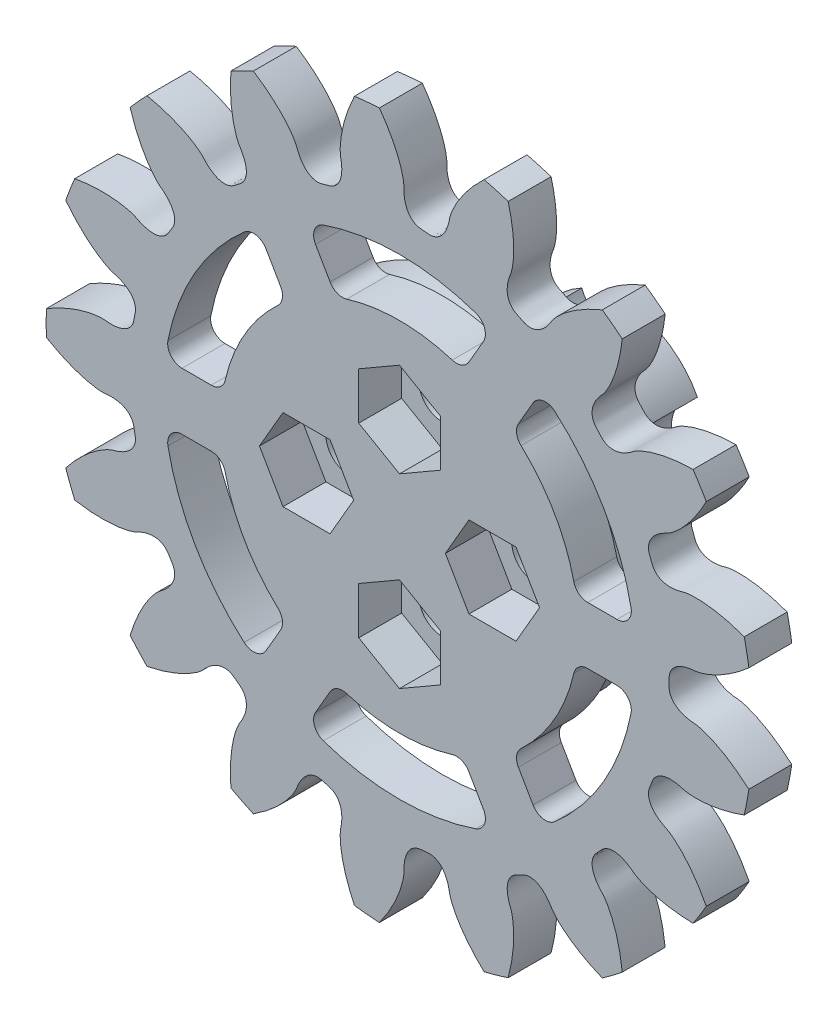
SolidWorks part; units mm, degrees
material "ABS"
ref_plane "前视基准面" through (0, 0, 0) normal (0, 0, 1) x (1, 0, 0)
ref_plane "上视基准面" through (0, 0, 0) normal (0, 1, 0) x (1, 0, 0)
ref_plane "右视基准面" through (0, 0, 0) normal (1, 0, 0) x (0, 0, -1)
sketch "草图1" plane through (0, 0, 0) normal (0, 0, 1) x (1, 0, 0)
  arc A0 (14.1766, -20.2266) -> (15.5749, -19.1706) centre (0, 0) ccw
  arc A1 (20.5259, -13.7396) -> (21.4484, -12.2498) centre (0, 0) ccw
  arc A2 (24.1032, -5.397) -> (24.4251, -3.6746) centre (0, 0) ccw
  arc A3 (24.4251, 3.6746) -> (24.1032, 5.397) centre (0, 0) ccw
  arc A4 (21.4484, 12.2498) -> (20.5259, 13.7396) centre (0, 0) ccw
  arc A5 (15.5749, 19.1706) -> (14.1766, 20.2266) centre (0, 0) ccw
  arc A6 (7.5979, 23.5024) -> (5.9126, 23.9819) centre (0, 0) ccw
  arc A7 (-1.4052, 24.66) -> (-3.15, 24.4983) centre (0, 0) ccw
  arc A8 (-10.2185, 22.4871) -> (-11.7871, 21.7061) centre (0, 0) ccw
  arc A9 (-17.6518, 17.2773) -> (-18.8323, 15.9824) centre (0, 0) ccw
  arc A10 (-22.7011, 9.734) -> (-23.3341, 8.1001) centre (0, 0) ccw
  arc A11 (-24.6845, 0.8761) -> (-24.6845, -0.8761) centre (0, 0) ccw
  arc A12 (-23.3341, -8.1001) -> (-22.7011, -9.734) centre (0, 0) ccw
  arc A13 (-18.8323, -15.9824) -> (-17.6518, -17.2773) centre (0, 0) ccw
  arc A14 (-11.7871, -21.7061) -> (-10.2185, -22.4871) centre (0, 0) ccw
  arc A15 (-3.15, -24.4983) -> (-1.4052, -24.66) centre (0, 0) ccw
  arc A16 (5.9126, -23.9819) -> (7.5979, -23.5024) centre (0, 0) ccw
  spline S0 degree 3 number of poles 73 (7.5979, -23.5024) -> (14.1766, -20.2266)
  spline S1 degree 3 number of poles 73 (15.5749, -19.1706) -> (20.5259, -13.7396)
  spline S2 degree 3 number of poles 73 (21.4484, -12.2498) -> (24.1032, -5.397)
  spline S3 degree 3 number of poles 73 (24.4251, -3.6746) -> (24.4251, 3.6746)
  spline S4 degree 3 number of poles 73 (24.1032, 5.397) -> (21.4484, 12.2498)
  spline S5 degree 3 number of poles 73 (20.5259, 13.7396) -> (15.5749, 19.1706)
  spline S6 degree 3 number of poles 73 (14.1766, 20.2266) -> (7.5979, 23.5024)
  spline S7 degree 3 number of poles 73 (5.9126, 23.9819) -> (-1.4052, 24.66)
  spline S8 degree 3 number of poles 73 (-3.15, 24.4983) -> (-10.2185, 22.4871)
  spline S9 degree 3 number of poles 73 (-11.7871, 21.7061) -> (-17.6518, 17.2773)
  spline S10 degree 3 number of poles 73 (-18.8323, 15.9824) -> (-22.7011, 9.734)
  spline S11 degree 3 number of poles 73 (-23.3341, 8.1001) -> (-24.6845, 0.8761)
  spline S12 degree 3 number of poles 73 (-24.6845, -0.8761) -> (-23.3341, -8.1001)
  spline S13 degree 3 number of poles 73 (-22.7011, -9.734) -> (-18.8323, -15.9824)
  spline S14 degree 3 number of poles 73 (-17.6518, -17.2773) -> (-11.7871, -21.7061)
  spline S15 degree 3 number of poles 73 (-10.2185, -22.4871) -> (-3.15, -24.4983)
  spline S16 degree 3 number of poles 73 (-1.4052, -24.66) -> (5.9126, -23.9819)
  dimension "D1" = 0
extrude "凸台-拉伸1" add sketch "草图1" along normal blind 5
sketch "草图2" plane through (0, 0, 0) normal (0, 0, -1) x (-1, 0, 0)
  circle A0 centre (0, 0) radius 10
  dimension "D1" = 20
extrude "凸台-拉伸2" add sketch "草图2" along normal blind 2.5
sketch "草图3" plane through (0, 0, 5) normal (0, 0, 1) x (1, 0, 0)
  line L0 (-16.5, 0) -> (-12.5, 0)
  line L1 (-8.25, 14.2894) -> (0, 0)
  line L2 (-16.5, -2) -> (-12.5, -2)
  line L3 (-9.9821, 13.2894) -> (-1.7321, -1)
  line L4 (-16.5, 2) -> (-12.5, 2)
  line L5 (-6.5179, 15.2894) -> (1.7321, 1)
  line L6 (-12.5, 2) -> (-8.75, 2)
  circle A0 centre (0, 0) radius 12.5
  circle A1 centre (0, 0) radius 16.5
  dimension "D1" = 25
  dimension "D2" = 4
  dimension "D3" = 60
  dimension "D4" = 2
  dimension "D5" = 2
extrude "切除-拉伸1" cut sketch "草图3" against normal blind 12 contours L3 A1 L4 L6 A0 region at (-12.3527, 7.1318, 5)
fillet "圆角1" radius 1 4 edges at (-12.339, 2, 2.5) (-9.9212, 13.1841, 2.5) (-7.9015, 9.6859, 2.5) (-16.3783, 2, 2.5)
pattern_circular "阵列(圆周)1" count 6 over 360 about axis through (0, 0, -2.5) along (0, 0, 1) of "圆角1", "切除-拉伸1"
sketch "草图4" plane through (0, 0, 0) normal (0, 0, -1) x (-1, 0, 0)
  circle A0 centre (0, 0) radius 12
  circle A1 centre (0, 0) radius 10 construction
  dimension "D1" = 2
extrude "凸台-拉伸3" add sketch "草图4" along normal blind 2.5
sketch "草图5" plane through (0, 0, -2.5) normal (0, 0, -1) x (-1, 0, 0)
  circle A0 centre (0, 0) radius 6
  circle A1 centre (0, 0) radius 3
  dimension "D1" = 12
  dimension "D2" = 6
extrude "凸台-拉伸4" add sketch "草图5" along normal blind 10
sketch "草图6" plane through (0, 0, -2.5) normal (0, 0, -1) x (-1, 0, 0)
  circle A0 centre (0, 0) radius 10
  circle A1 centre (0, 0) radius 6
  dimension "D1" = 20
extrude "凸台-拉伸6" add sketch "草图6" along normal blind 1.9
sketch "草图7" plane through (0, 0, 5) normal (0, 0, 1) x (1, 0, 0)
  arc A17 (14.1766, -20.2266) -> (15.5749, -19.1706) centre (0, 0) ccw
  arc A18 (20.5259, -13.7396) -> (21.4484, -12.2498) centre (0, 0) ccw
  arc A19 (24.1032, -5.397) -> (24.4251, -3.6746) centre (0, 0) ccw
  arc A20 (24.4251, 3.6746) -> (24.1032, 5.397) centre (0, 0) ccw
  arc A21 (21.4484, 12.2498) -> (20.5259, 13.7396) centre (0, 0) ccw
  arc A22 (15.5749, 19.1706) -> (14.1766, 20.2266) centre (0, 0) ccw
  arc A23 (7.5979, 23.5024) -> (5.9126, 23.9819) centre (0, 0) ccw
  arc A24 (-1.4052, 24.66) -> (-3.15, 24.4983) centre (0, 0) ccw
  arc A25 (-10.2185, 22.4871) -> (-11.7871, 21.7061) centre (0, 0) ccw
  arc A26 (-17.6518, 17.2773) -> (-18.8323, 15.9824) centre (0, 0) ccw
  arc A27 (-22.7011, 9.734) -> (-23.3341, 8.1001) centre (0, 0) ccw
  arc A28 (-24.6845, 0.8761) -> (-24.6845, -0.8761) centre (0, 0) ccw
  arc A29 (-23.3341, -8.1001) -> (-22.7011, -9.734) centre (0, 0) ccw
  arc A30 (-18.8323, -15.9824) -> (-17.6518, -17.2773) centre (0, 0) ccw
  arc A31 (-11.7871, -21.7061) -> (-10.2185, -22.4871) centre (0, 0) ccw
  arc A32 (-3.15, -24.4983) -> (-1.4052, -24.66) centre (0, 0) ccw
  arc A33 (5.9126, -23.9819) -> (7.5979, -23.5024) centre (0, 0) ccw
  arc A34 (14.1766, -20.2266) -> (15.5749, -19.1706) centre (0, 0) ccw
  arc A35 (20.5259, -13.7396) -> (21.4484, -12.2498) centre (0, 0) ccw
  arc A36 (24.1032, -5.397) -> (24.4251, -3.6746) centre (0, 0) ccw
  arc A37 (24.4251, 3.6746) -> (24.1032, 5.397) centre (0, 0) ccw
  arc A38 (21.4484, 12.2498) -> (20.5259, 13.7396) centre (0, 0) ccw
  arc A39 (15.5749, 19.1706) -> (14.1766, 20.2266) centre (0, 0) ccw
  arc A40 (7.5979, 23.5024) -> (5.9126, 23.9819) centre (0, 0) ccw
  arc A41 (-1.4052, 24.66) -> (-3.15, 24.4983) centre (0, 0) ccw
  arc A42 (-10.2185, 22.4871) -> (-11.7871, 21.7061) centre (0, 0) ccw
  arc A43 (-17.6518, 17.2773) -> (-18.8323, 15.9824) centre (0, 0) ccw
  arc A44 (-22.7011, 9.734) -> (-23.3341, 8.1001) centre (0, 0) ccw
  arc A45 (-24.6845, 0.8761) -> (-24.6845, -0.8761) centre (0, 0) ccw
  arc A46 (-23.3341, -8.1001) -> (-22.7011, -9.734) centre (0, 0) ccw
  arc A47 (-18.8323, -15.9824) -> (-17.6518, -17.2773) centre (0, 0) ccw
  arc A48 (-11.7871, -21.7061) -> (-10.2185, -22.4871) centre (0, 0) ccw
  arc A49 (-3.15, -24.4983) -> (-1.4052, -24.66) centre (0, 0) ccw
  arc A50 (5.9126, -23.9819) -> (7.5979, -23.5024) centre (0, 0) ccw
  spline S17 degree 3 number of poles 73 (7.5979, -23.5024) -> (14.1766, -20.2266)
  spline S18 degree 3 number of poles 73 (15.5749, -19.1706) -> (20.5259, -13.7396)
  spline S19 degree 3 number of poles 73 (21.4484, -12.2498) -> (24.1032, -5.397)
  spline S20 degree 3 number of poles 73 (24.4251, -3.6746) -> (24.4251, 3.6746)
  spline S21 degree 3 number of poles 73 (24.1032, 5.397) -> (21.4484, 12.2498)
  spline S22 degree 3 number of poles 73 (20.5259, 13.7396) -> (15.5749, 19.1706)
  spline S23 degree 3 number of poles 73 (14.1766, 20.2266) -> (7.5979, 23.5024)
  spline S24 degree 3 number of poles 73 (5.9126, 23.9819) -> (-1.4052, 24.66)
  spline S25 degree 3 number of poles 73 (-3.15, 24.4983) -> (-10.2185, 22.4871)
  spline S26 degree 3 number of poles 73 (-11.7871, 21.7061) -> (-17.6518, 17.2773)
  spline S27 degree 3 number of poles 73 (-18.8323, 15.9824) -> (-22.7011, 9.734)
  spline S28 degree 3 number of poles 73 (-23.3341, 8.1001) -> (-24.6845, 0.8761)
  spline S29 degree 3 number of poles 73 (-24.6845, -0.8761) -> (-23.3341, -8.1001)
  spline S30 degree 3 number of poles 73 (-22.7011, -9.734) -> (-18.8323, -15.9824)
  spline S31 degree 3 number of poles 73 (-17.6518, -17.2773) -> (-11.7871, -21.7061)
  spline S32 degree 3 number of poles 73 (-10.2185, -22.4871) -> (-3.15, -24.4983)
  spline S33 degree 3 number of poles 73 (-1.4052, -24.66) -> (5.9126, -23.9819)
  spline S34 degree 3 number of poles 73 (7.5979, -23.5024) -> (14.1766, -20.2266)
  spline S35 degree 3 number of poles 73 (15.5749, -19.1706) -> (20.5259, -13.7396)
  spline S36 degree 3 number of poles 73 (21.4484, -12.2498) -> (24.1032, -5.397)
  spline S37 degree 3 number of poles 73 (24.4251, -3.6746) -> (24.4251, 3.6746)
  spline S38 degree 3 number of poles 73 (24.1032, 5.397) -> (21.4484, 12.2498)
  spline S39 degree 3 number of poles 73 (20.5259, 13.7396) -> (15.5749, 19.1706)
  spline S40 degree 3 number of poles 73 (14.1766, 20.2266) -> (7.5979, 23.5024)
  spline S41 degree 3 number of poles 73 (5.9126, 23.9819) -> (-1.4052, 24.66)
  spline S42 degree 3 number of poles 73 (-3.15, 24.4983) -> (-10.2185, 22.4871)
  spline S43 degree 3 number of poles 73 (-11.7871, 21.7061) -> (-17.6518, 17.2773)
  spline S44 degree 3 number of poles 73 (-18.8323, 15.9824) -> (-22.7011, 9.734)
  spline S45 degree 3 number of poles 73 (-23.3341, 8.1001) -> (-24.6845, 0.8761)
  spline S46 degree 3 number of poles 73 (-24.6845, -0.8761) -> (-23.3341, -8.1001)
  spline S47 degree 3 number of poles 73 (-22.7011, -9.734) -> (-18.8323, -15.9824)
  spline S48 degree 3 number of poles 73 (-17.6518, -17.2773) -> (-11.7871, -21.7061)
  spline S49 degree 3 number of poles 73 (-10.2185, -22.4871) -> (-3.15, -24.4983)
  spline S50 degree 3 number of poles 73 (-1.4052, -24.66) -> (5.9126, -23.9819)
  dimension "D1" = 0
extrude "切除-拉伸2" cut sketch "草图7" against normal blind 2
sketch "草图8" plane through (0, 0, -4.4) normal (0, 0, -1) x (-1, 0, 0)
  circle A0 centre (0, 0) radius 6.5
  circle A1 centre (-6.5, 0) radius 1.65
  circle A2 centre (-6.5, 0) radius 3
  circle M2 centre (0, 0) radius 6
  dimension "D1" = 3.3
  dimension "D2" = 13
  dimension "D3" = 6
extrude "切除-拉伸3" cut sketch "草图8" against normal mid plane 30 contours A0 A1 | A1 A0 M2 | A1 M2 region at (6.1858, 0, -4.4) region at (7.1612, 0, -4.4) region at (5.4878, 0, -4.4)
ref_plane "基准面1" through (0, 0, -7.4) normal (0, 0, -1) x (-1, 0, 0)
sketch "草图9" plane through (0, 0, -7.4) normal (0, 0, -1) x (-1, 0, 0)
  circle A0 centre (-6.5, 0) radius 3
  dimension "D1" = 6
extrude "切除-拉伸4" cut sketch "草图9" along normal blind 10
sketch "草图10" plane through (0, 0, -7.4) normal (0, 0, -1) x (-1, 0, 0)
  circle A0 centre (-6.5, 0) radius 3
extrude "切除-拉伸6" cut sketch "草图10" against normal blind 2
pattern_circular "阵列(圆周)2" count 4 over 360 about axis through (0, 0, -12.5) along (0, 0, 1) of "切除-拉伸4", "切除-拉伸3", "切除-拉伸6" reverse direction yes
sketch "草图11" plane through (0, 0, 3) normal (0, 0, 1) x (1, 0, 0)
  line L1 (-3.2091, 0) -> (-4.8546, 2.85)
  line L2 (-4.8546, 2.85) -> (-8.1454, 2.85)
  line L3 (-8.1454, 2.85) -> (-9.7909, 0)
  line L4 (-9.7909, 0) -> (-8.1454, -2.85)
  line L5 (-8.1454, -2.85) -> (-4.8546, -2.85)
  line L6 (-4.8546, -2.85) -> (-3.2091, 0)
  circle A0 centre (-6.5, 0) radius 2.85 construction
  dimension "D1" = 5.7
extrude "切除-拉伸7" cut sketch "草图11" against normal blind 3
pattern_circular "阵列(圆周)3" count 4 over 360 about axis through (0, 0, 5) along (0, 0, -1) of "切除-拉伸7"
